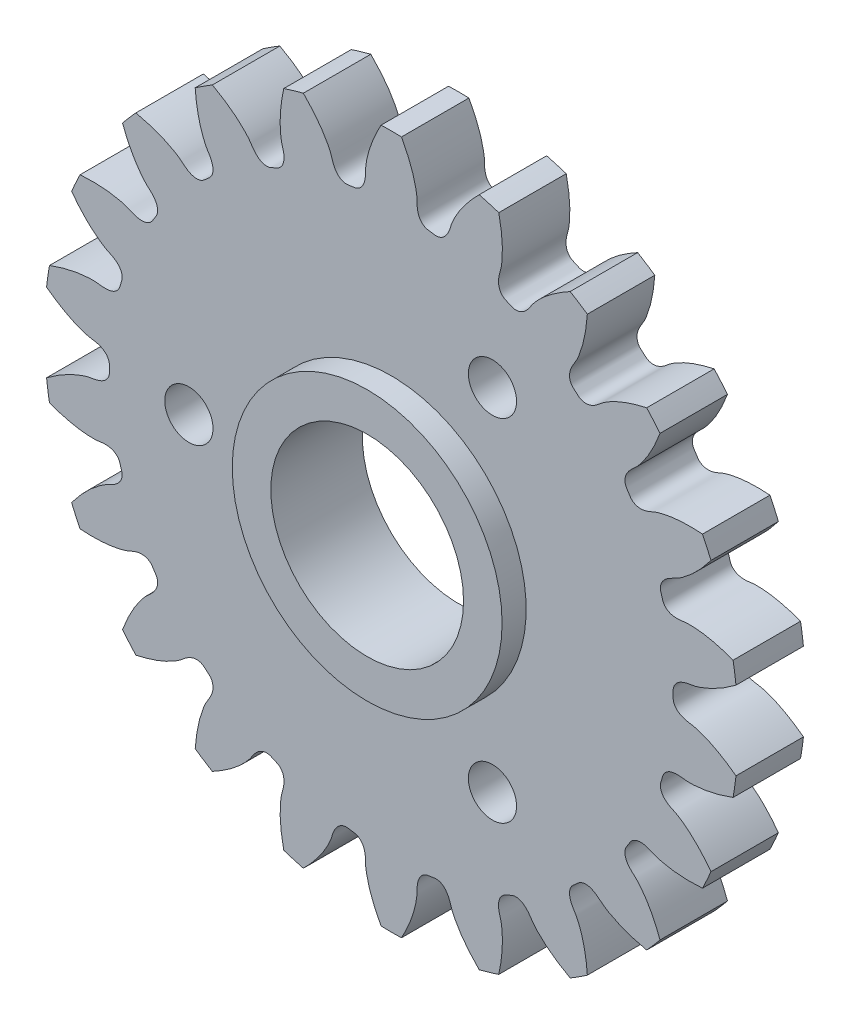
SolidWorks part; units mm, degrees
note: '?' marks a value the reader was unsure of.
material "POM 乙缩醛共聚物"
ref_plane "Front" through (0, 0, 0) normal (0, 0, 1) x (1, 0, 0)
ref_plane "Top" through (0, 0, 0) normal (0, 1, 0) x (1, 0, 0)
ref_plane "Right" through (0, 0, 0) normal (1, 0, 0) x (0, 0, -1)
ref_axis "基准轴1" through (0, 0, 50) along (0, 0, -1)?
sketch "旋转草图小直齿轮" plane through (0, 0, 0) normal (1, 0, 0) x (0, 0, -1)
  line L0 (0, 0) -> (1, 0) construction
  line L1 (-3.5, 0) -> (-3.5, 36)
  line L2 (-3.5, 36) -> (3.5, 36)
  line L3 (3.5, 36) -> (3.5, 0)
  line L4 (3.5, 0) -> (-3.5, 0)
  dimension "Side1" = 3.5
  dimension "OutsideRadius" = 36
  dimension "Side2" = 3.5
revolve "小直齿轮" add sketch "旋转草图小直齿轮" angle 360 about L0
sketch "齿草图小直齿轮" plane through (0, 0, 0) normal (0, 0, 1) x (1, 0, 0)
  arc A0 (35.9077, 4.1788) -> (35.9077, -4.1788) centre (0, 0) cw
  spline S0 degree 3 poles (35.9077, -4.1788) (35.6282, -3.9638) (35.2112, -3.6615) (34.6529, -3.2947) (34.2616, -3.0542) (33.8875, -2.8393) (33.5317, -2.6489) (33.1952, -2.4816) (32.8792, -2.336) (32.5846, -2.2109) (32.3123, -2.1047) (32.0632, -2.0161) (31.838, -1.9435) (31.6375, -1.8853) (31.4623, -1.8401) (31.313, -1.8064) (31.0856, -1.7615) (30.8773, -1.7399) (30.6862, -1.7011) (30.6048, -1.6827) (30.5252, -1.6626) (30.4472, -1.6407) (30.3707, -1.6169) (30.2957, -1.5912) (30.222, -1.5634) (30.1497, -1.5333) (30.0785, -1.5008) (30.0084, -1.4655) (29.9393, -1.4272) (29.8711, -1.3856) (29.8038, -1.34) (29.7374, -1.2901) (29.6721, -1.2352) (29.608, -1.1745) (29.5456, -1.1074) (29.4856, -1.0329) (29.4289, -0.9506) (29.3768, -0.8597) (29.3311, -0.7602) (29.2935, -0.6526) (29.2659, -0.5378) (29.2514, -0.426) (29.2451, -0.2461) (29.2537, 0) (29.2451, 0.2461) (29.2514, 0.426) (29.2659, 0.5378) (29.2935, 0.6526) (29.3311, 0.7602) (29.3768, 0.8597) (29.4289, 0.9506) (29.4856, 1.0329) (29.5456, 1.1074) (29.608, 1.1745) (29.6721, 1.2352) (29.7374, 1.2901) (29.8038, 1.34) (29.8711, 1.3856) (29.9393, 1.4272) (30.0084, 1.4655) (30.0785, 1.5008) (30.1497, 1.5333) (30.222, 1.5634) (30.2957, 1.5912) (30.3707, 1.6169) (30.4472, 1.6407) (30.5252, 1.6626) (30.6048, 1.6827) (30.6862, 1.7011) (30.8773, 1.7399) (31.0856, 1.7615) (31.313, 1.8064) (31.4623, 1.8401) (31.6375, 1.8853) (31.838, 1.9435) (32.0632, 2.0161) (32.3123, 2.1047) (32.5846, 2.2109) (32.8792, 2.336) (33.1952, 2.4816) (33.5317, 2.6489) (33.8875, 2.8393) (34.2616, 3.0542) (34.6529, 3.2947) (35.2112, 3.6615) (35.6282, 3.9638) (35.9077, 4.1788) knots 0 0 0 0 0.063463 0.092689 0.120245 0.146131 0.170347 0.192893 0.213769 0.232975 0.25051 0.266376 0.280572 0.293097 0.303953 0.313138 0.320653 0.345676 0.350759 0.35576 0.360686 0.365546 0.370347 0.375102 0.37982 0.384517 0.389207 0.393908 0.39864 0.403426 0.40829 0.413262 0.418372 0.423652 0.429137 0.43486 0.440848 0.447122 0.453688 0.460533 0.467623 0.474898 0.480792 0.5 0.519208 0.525102 0.532377 0.539467 0.546312 0.552878 0.559152 0.56514 0.570863 0.576348 0.581628 0.586738 0.59171 0.596574 0.60136 0.606092 0.610793 0.615483 0.62018 0.624898 0.629653 0.634454 0.639314 0.64424 0.649241 0.654324 0.679347 0.686862 0.696047 0.706903 0.719428 0.733624 0.74949 0.767025 0.786231 0.807107 0.829653 0.853869 0.879755 0.907311 0.936537 1 1 1 1
extrude "齿拉伸切除小直齿轮" cut sketch "齿草图小直齿轮" against normal through all and the other way through all
pattern_circular "齿形小直齿轮" count 22 every 16.364 about axis through (0, 0, 50) along (0, 0, -1) of "齿拉伸切除小直齿轮"
sketch "辅助草图小直齿轮" plane through (0, 0, 0) normal (0, 0, 1) x (1, 0, 0)
  circle A0 centre (0, 0) radius 33 construction
  circle A1 centre (0, 0) radius 31.0099 construction
  circle A2 centre (0, 0) radius 31.0778 construction
  circle A3 centre (0, 0) radius 36 construction
  circle A4 centre (0, 0) radius 29.25 construction
  dimension "PitchDiameter" = 66
  dimension "BaseDiameter" = 62.0197
  dimension "FormDiameter" = 62.1556
  dimension "MajorDiameter" = 72
  dimension "MinorDiameter" = 58.5
sketch "草图5" plane through (0, 0, 3.5) normal (0, 0, 1) x (1, 0, 0)
  circle A0 centre (0, 0) radius 25 construction
  circle A1 centre (-3.4822, 24.7563) radius 2.5
  circle A2 centre (23.1807, -9.3625) radius 2.5
  circle A3 centre (-19.6985, -15.3938) radius 2.5
  point P11 (0, 0)
  dimension "D1" = 50
  dimension "D2" = 5
  dimension "D3" = 3
extrude "切除-拉伸2" [suppressed] cut sketch "草图5" against normal through all
hole_wizard "打孔尺寸(%根据十字)槽沉头木螺钉的类型1" [suppressed] positions "3D草图1" profile "草图6" countersink size "M5" standard "GB"
sketch3d "3D草图1" [suppressed]
  line L0 (-3.4822, 24.7563, -2.5) -> (-3.4822, 24.7563, 2.5) construction
  line L1 (-19.6985, -15.3938, -2.5) -> (-19.6985, -15.3938, 2.5) construction
  line L2 (23.1807, -9.3625, -2.5) -> (23.1807, -9.3625, 2.5) construction
  point P0 (-3.4822, 24.7563, 2.5)
  point P5 (-19.6985, -15.3938, 2.5)
  point P9 (23.1807, -9.3625, 2.5)
sketch "草图6" plane through (-3.4822, 24.7563, 2.5) normal (1, 0, 0) x (0, -1, 0)
  line L0 (0, 0) -> (0, 5)
  line L1 (0, 5) -> (2.5, 5)
  line L2 (2.5, 5) -> (2.5, 1.75)
  line L3 (2.5, 1.75) -> (4.25, 0)
  line L5 (4.25, 0) -> (0, 0)
  line L6 (-2.5, 1.75) -> (-4.25, 0) construction
  line L11 (0, -6.35) -> (0, 107.95) construction
  dimension "通孔孔直径" = 5
  dimension "通孔孔深度" = 5
  dimension "近端锥形沉头孔直径" = 8.5
  dimension "近端锥形沉头孔角度" = 90
sketch "草图7" [suppressed] plane through (0, 0, 2.5) normal (0, 0, 1) x (1, 0, 0)
  line L0 (-18.0809, 7.3027) -> (0, 0) construction
  line L1 (0, 0) -> (-3.4822, 24.7563) construction
  circle A0 centre (0, 0) radius 10
  circle A1 centre (0, 0) radius 19.5 construction
  circle A3 centre (-18.0809, 7.3027) radius 5
  circle A4 centre (15.3648, 12.0072) radius 5
  circle A5 centre (2.7161, -19.3099) radius 5
  point P14 (0, 0)
  dimension "D1" = 20
  dimension "D2" = 39
  dimension "D3" = 10
  dimension "D4" = 60
  dimension "D5" = 3
extrude "切除-拉伸3" [suppressed] cut sketch "草图7" against normal blind 10
sketch "草图8" plane through (0, 0, 3.5) normal (0, 0, 1) x (1, 0, 0)
  line L0 (-10.5, -18.1865) -> (0, 0) construction
  line L1 (0, 0) -> (21, 0) construction
  circle A0 centre (0, 0) radius 21 construction
  circle A1 centre (-21, 0) radius 2.5
  circle A2 centre (10.5, 18.1865) radius 2.5
  circle A3 centre (10.5, -18.1865) radius 2.5
  circle A4 centre (0, 0) radius 10
  circle A5 centre (-10.5, -18.1865) radius 5 construction
  circle A6 centre (-10.5, 18.1865) radius 5 construction
  circle A7 centre (21, 0) radius 5 construction
  circle A8 centre (-21, 0) radius 5 construction
  point P11 (0, 0)
  dimension "D1" = 42
  dimension "D3" = 5
  dimension "D4" = 20
  dimension "D6" = 10
  dimension "D7" = 10
  dimension "D5" = 120
  dimension "D2" = 3
extrude "切除-拉伸4" cut sketch "草图8" against normal blind 10
sketch "草图9" plane through (0, 0, 3.5) normal (0, 0, 1) x (1, 0, 0)
  circle A0 centre (0, 0) radius 10 construction
  circle A1 centre (0, 0) radius 10
  circle A2 centre (0, 0) radius 14
  dimension "D1" = 4
extrude "凸台-拉伸1" add sketch "草图9" along normal blind 2.5
hole_wizard "打孔尺寸(%根据十字)槽沉头木螺钉的类型2" positions "3D草图2" profile "草图10" countersink size "M5" standard "GB" end condition through all
sketch3d "3D草图2"
  line L0 (-21, 0, -3.5) -> (-21, 0, 3.5) construction
  line L1 (10.5, -18.1865, -3.5) -> (10.5, -18.1865, 3.5) construction
  line L2 (10.5, 18.1865, -3.5) -> (10.5, 18.1865, 3.5) construction
  point P0 (-21, 0, -3.5)
  point P4 (10.5, -18.1865, -3.5)
  point P8 (10.5, 18.1865, -3.5)
sketch "草图10" plane through (-21, 0, -3.5) normal (1, 0, 0) x (0, 1, 0)
  line L0 (0, 0) -> (0, 9.5)
  line L1 (0, 9.5) -> (2.5, 9.5)
  line L2 (2.5, 9.5) -> (2.5, 3.1)
  line L3 (2.5, 3.1) -> (5.6, 0)
  line L5 (5.6, 0) -> (0, 0)
  line L6 (-2.5, 3.1) -> (-5.6, 0) construction
  line L11 (0, -6.35) -> (0, 107.95) construction
  dimension "通孔孔直径" = 5
  dimension "通孔孔深度" = 9.5
  dimension "近端锥形沉头孔直径" = 11.2
  dimension "近端锥形沉头孔角度" = 90
